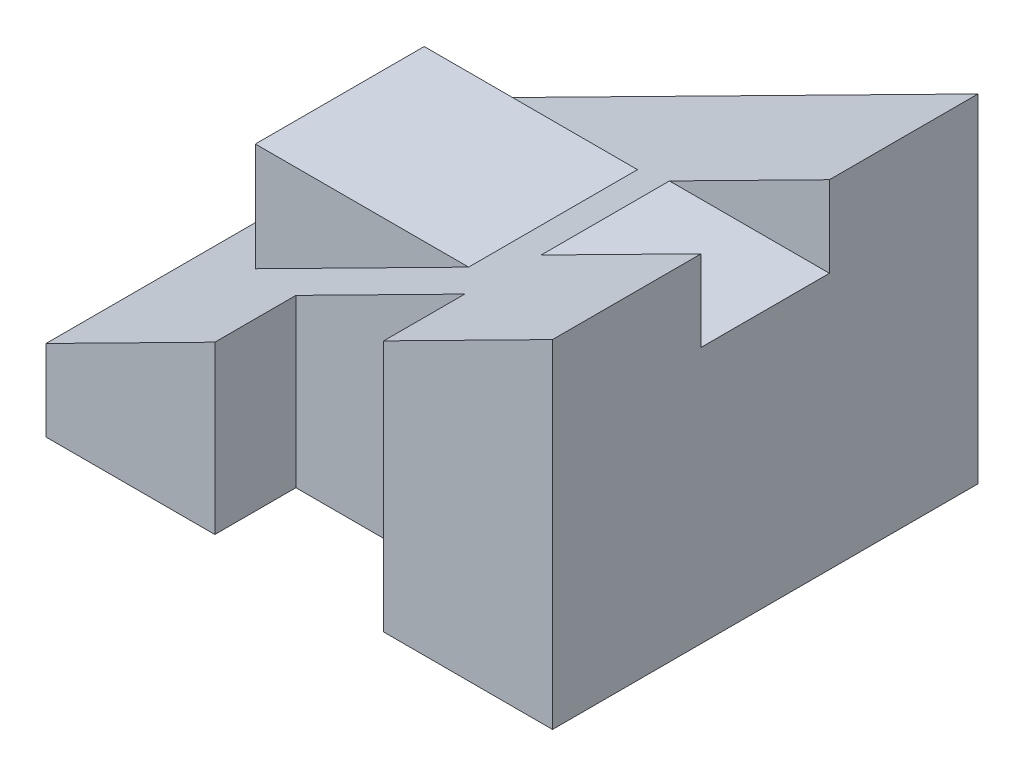
SolidWorks part; units mm, degrees
ref_plane "Front Plane" through (0, 0, 0) normal (0, 0, 1) x (1, 0, 0)
ref_plane "Top Plane" through (0, 0, 0) normal (0, 1, 0) x (1, 0, 0)
ref_plane "Right Plane" through (0, 0, 0) normal (1, 0, 0) x (0, 0, -1)
sketch "Sketch1" plane through (0, 0, 0) normal (0, 0, 1) x (1, 0, 0)
  line L0 (0, 0) -> (-75, 0)
  line L1 (-75, 0) -> (-75, 12)
  line L2 (-75, 12) -> (0, 50)
  line L3 (0, 50) -> (0, 0)
  line L4 (-25, 37.3333) -> (-25, 0)
  line L5 (-50, 24.6667) -> (-50, 0)
  line L6 (0, 38) -> (-23.6842, 38)
  line L7 (-63, 18.08) -> (-63, 34.08)
  line L8 (-63, 34.08) -> (-31.4211, 34.08)
  dimension "D1" = 75
  dimension "D2" = 50
  dimension "D3" = 25
  dimension "D4" = 25
  dimension "D5" = 12
  dimension "D6" = 12
  dimension "D7" = 16
  dimension "D8" = 12
extrude "Boss-Extrude1" add sketch "Sketch1" against normal blind 63 contours L5 L2 L1 L0 | L3 L6 L2 L4 L0 region at (-12.4944, 18.9913, 0) region at (-61.0606, 9.5313, 0)
extrude "Boss-Extrude2" add sketch "Sketch1<3>" against normal blind 51 from offset 12 contours L2 L5 L0 L4 region at (-36.6487, 15.7157, 0) offset against normal yes
sketch "Sketch1<3>" plane through (0, 0, 0) normal (0, 0, 1) x (1, 0, 0) same geometry as "Sketch1"
extrude "Boss-Extrude3" add sketch "Sketch1<4>" against normal blind 25 from offset 19 contours L8 L7 L2 region at (-52.4737, 28.7467, 0) offset against normal yes
sketch "Sketch1<4>" plane through (0, 0, 0) normal (0, 0, 1) x (1, 0, 0) same geometry as "Sketch1"
extrude "Boss-Extrude4" add sketch "Sketch1<5>" against normal blind 22 from offset 41 contours L6 L3 L2 region at (-7.8947, 42, 0) offset against normal yes
sketch "Sketch1<5>" plane through (0, 0, 0) normal (0, 0, 1) x (1, 0, 0) same geometry as "Sketch1"
extrude "Boss-Extrude5" add sketch "Sketch1<6>" against normal blind 22 contours L6 L3 L2 region at (-7.8947, 42, 0)
sketch "Sketch1<6>" plane through (0, 0, 0) normal (0, 0, 1) x (1, 0, 0) same geometry as "Sketch1"
